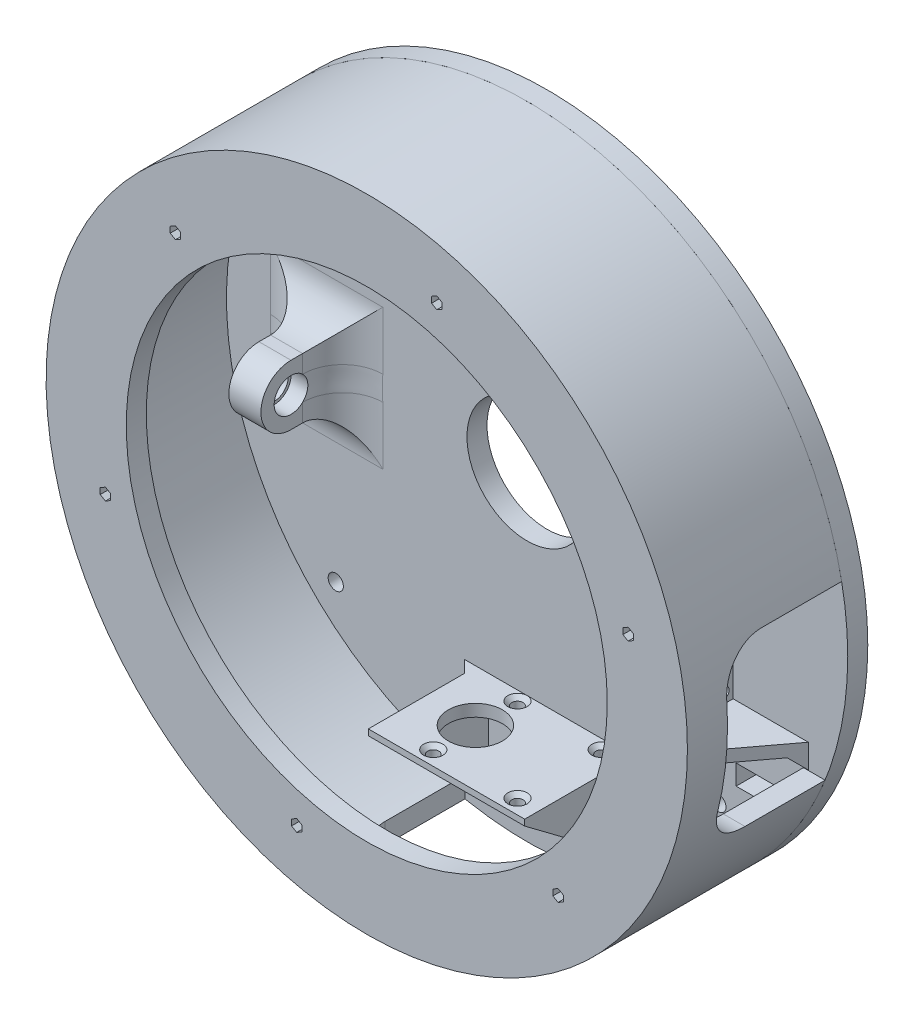
SolidWorks part; units mm, degrees
ref_plane "正面" through (0, 0, 0) normal (0, 0, 1) x (1, 0, 0)
ref_plane "平面" through (0, 0, 0) normal (0, 1, 0) x (1, 0, 0)
ref_plane "右側面" through (0, 0, 0) normal (1, 0, 0) x (0, 0, -1)
sketch "ｽｹｯﾁ5" plane through (0, 0, 0) normal (0, 1, 0) x (1, 0, 0)
  line L0 (48.4, -32) -> (48.4, 0)
  line L1 (48.4, 0) -> (72.4, 0)
  line L2 (72.4, 0) -> (48.4, -32)
  line L3 (-88, 0) -> (88, 0) construction
  dimension "D1" = 24
  dimension "D2" = 32
  dimension "D3" = 48.4
extrude "ﾎﾞｽ - 押し出し3" add sketch "ｽｹｯﾁ5" along normal blind 39 from offset 26.4 offset against normal yes
shell "ｼｪﾙ2" thickness 3
sketch "ｽｹｯﾁ7" plane through (51.4, 0, 0) normal (1, 0, 0) x (0, 0, -1)
  line L0 (-3, 9.6) -> (-3, -23.4) construction
  line L1 (-26.4, -21) -> (-5.4, -21) construction
  line L2 (-26.4, -21) -> (-26.4, 0) construction
  line L3 (-26.4, 0) -> (-5.4, 0) construction
  line L4 (-5.4, -21) -> (-5.4, 0) construction
  line L7 (-3, -23.4) -> (-28, -23.4) construction
  circle A0 centre (-15.9, 0) radius 6.75
  circle A1 centre (-26.4, -21) radius 1.4
  circle A2 centre (-5.4, -21) radius 1.4
  circle A3 centre (-5.4, 0) radius 1.4
  circle A4 centre (-26.4, 0) radius 1.4
  dimension "D3" = 2.8
  dimension "D6" = 13.5
  dimension "D1" = 21
  dimension "D2" = 21
  dimension "D4" = 2.4
  dimension "D5" = 2.4
extrude "ｶｯﾄ - 押し出し5" cut sketch "ｽｹｯﾁ7" against normal through all
sketch "ｽｹｯﾁ12" plane through (0, 0, 0) normal (0, 0, 1) x (1, 0, 0)
  line L0 (48.4, 12.6) -> (48.4, -26.4) construction
  line L1 (48.4, 12.6) -> (48.4, -26.4)
  line L2 (48.4, -26.4) -> (86.6023, -26.4)
  line L3 (72.4, -26.4) -> (48.4, -26.4) construction
  line L4 (86.6023, -26.4) -> (86.6023, 12.6)
  line L5 (86.6023, 12.6) -> (48.4, 12.6)
  line L6 (72.4, 12.6) -> (48.4, 12.6) construction
extrude "ｶｯﾄ - 押し出し14" cut sketch "ｽｹｯﾁ12" along normal blind 10 from offset 30
sketch "ｽｹｯﾁ18" plane through (48.4, 0, 0) normal (-1, 0, 0) x (0, 0, 1)
  circle A0 centre (26.4, 0) radius 2.4
  circle A1 centre (26.4, -21) radius 2.4
  circle A2 centre (5.4, 0) radius 2.4
  circle A3 centre (5.4, -21) radius 2.4
  dimension "D1" = 4.8
extrude "ｶｯﾄ - 押し出し15" cut sketch "ｽｹｯﾁ18" against normal blind 1.2 draft 45
sketch "ｽｹｯﾁ1" plane through (0, 0, 0) normal (0, 0, 1) x (1, 0, 0)
  line L1 (56.5685, -56.5685) -> (-56.5685, -56.5685) construction
  line L2 (56.5685, -56.5685) -> (56.5685, 56.5685) construction
  line L3 (56.5685, 56.5685) -> (-56.5685, 56.5685) construction
  line L4 (-56.5685, -56.5685) -> (-56.5685, 56.5685) construction
  line L5 (56.5685, -56.5685) -> (-56.5685, 56.5685) construction
  line L6 (56.5685, 56.5685) -> (-56.5685, -56.5685) construction
  circle A0 centre (0, 0) radius 80
  point P0 (0, 0)
  dimension "D1" = 160
extrude "ﾎﾞｽ - 押し出し1" add sketch "ｽｹｯﾁ1" along normal blind 3 and the other way blind 2 contours A0
sketch "ｽｹｯﾁ3" plane through (0, 0, 0) normal (0, 0, 1) x (1, 0, 0)
  circle A0 centre (0, 0) radius 15
  dimension "D1" = 30
extrude "ｶｯﾄ - 押し出し4" cut sketch "ｽｹｯﾁ3" against normal through all both and the other way through all
ref_plane "平面1" through (0, 54, 0) normal (0, 1, 0) x (1, 0, 0)
sketch "ｽｹｯﾁ10" plane through (-147.416, 54, 0) normal (0, 1, 0) x (1, 0, 0)
  line L0 (139.916, 0) -> (154.916, 0)
  line L1 (154.916, 0) -> (154.916, -15.9)
  line L2 (139.916, 0) -> (139.916, -15.9)
  line L3 (59.416, 0) -> (235.416, 0) construction
  arc A2 (139.916, -15.9) -> (154.916, -15.9) centre (147.416, -15.9) ccw
  point P7 (147.416, 0)
  dimension "D1" = 15
  dimension "D2" = 15.9
extrude "ﾎﾞｽ - 押し出し5" add sketch "ｽｹｯﾁ10" against normal blind 8
sketch "ｽｹｯﾁ11" plane through (-147.416, 54, 0) normal (0, 1, 0) x (1, 0, 0)
  circle A0 centre (147.416, -15.9) radius 4.2
  arc A1 (139.916, -15.9) -> (154.916, -15.9) centre (147.416, -15.9) ccw construction
  dimension "D1" = 8.4
extrude "ｶｯﾄ - 押し出し8" cut sketch "ｽｹｯﾁ11" along normal up to surface (8 mm away)
sketch "ｽｹｯﾁ14" plane through (0, 54, 0) normal (0, -1, 0) x (1, 0, 0)
  circle A0 centre (0, 15.9) radius 4.2 construction
  circle A1 centre (0, 15.9) radius 4.2
  circle A2 centre (0, 15.9) radius 3.5
  dimension "D1" = 7
extrude "ﾎﾞｽ - 押し出し6" add sketch "ｽｹｯﾁ14" along normal offset from surface (3.8 mm away) 4.2 up to face at (0, 46, 20.1)
fillet "ﾌｨﾚｯﾄ1" radius 10 4 edges at (7.5, 50, 3) (-7.5, 50, 3) (0, 46, 3) (0, 54, 3)
ref_plane "平面3" through (0, 0, 0) normal (0.7071, 0.7071, 0) x (-0.7071, 0.7071, 0)
mirror "ﾐﾗｰ1" about plane through (0, 0, 0) normal (0.7071, 0.7071, 0) of bodies 135 129
sketch "ｽｹｯﾁ15" plane through (0, 0, 3) normal (0, 0, 1) x (1, 0, 0)
  line L0 (-6.75, -51.4) -> (6.75, -51.4) construction
  line L1 (3.85, -68.1) -> (17.65, -68.1)
  line L2 (3.85, -68.1) -> (3.85, -74.4)
  line L3 (3.85, -74.4) -> (17.65, -74.4)
  line L4 (17.65, -68.1) -> (17.65, -74.4)
  line L5 (3.85, -68.1) -> (17.65, -74.4) construction
  line L6 (3.85, -74.4) -> (17.65, -68.1) construction
  line L7 (-6.75, -51.4) -> (6.75, -51.4)
  line L8 (88, -88) -> (-88, 88) construction
  line L9 (74.4, -3.85) -> (68.1, -17.65) construction
  line L10 (68.1, -3.85) -> (74.4, -17.65) construction
  line L11 (68.1, -17.65) -> (74.4, -17.65) construction
  line L12 (74.4, -3.85) -> (74.4, -17.65) construction
  line L13 (68.1, -3.85) -> (74.4, -3.85) construction
  line L14 (68.1, -3.85) -> (68.1, -17.65) construction
  point P0 (10.75, -71.25)
  point P7 (0, -51.4)
  point P14 (71.25, -10.75)
  dimension "D1" = 3.85
  dimension "D2" = 23
  dimension "D3" = 17.65
  dimension "D4" = 6.3
extrude "ｶｯﾄ - 押し出し11" cut sketch "ｽｹｯﾁ15" along normal through all both and the other way through all contours L12 L11 L14 L13 | L2 L1 L4 L3
sketch "ｽｹｯﾁ16" plane through (0, 0, 3) normal (0, 0, 1) x (1, 0, 0)
  line L0 (56.5685, 56.5685) -> (-56.5685, -56.5685) construction
  circle A0 centre (0, 0) radius 67.5 construction
  circle A1 centre (-47.7297, -47.7297) radius 1.9
  circle A3 centre (-47.7297, 47.7297) radius 1.9
  circle A4 centre (47.7297, 47.7297) radius 1.9
  circle A5 centre (47.7297, -47.7297) radius 1.9
  point P14 (0, 0)
  dimension "D1" = 135
  dimension "D3" = 3.8
  dimension "D2" = 4
extrude "ｶｯﾄ - 押し出し12" cut sketch "ｽｹｯﾁ16" against normal through all both and the other way through all
chamfer "面取り1" distance 3 angle 45 4 edges at (-12.6, -59.275, 3) (26.4, -59.275, 3) (59.275, -26.4, 3) (59.275, 12.6, 3)
sketch "ｽｹｯﾁ17" plane through (0, 0, 3) normal (0, 0, 1) x (1, 0, 0)
  line L1 (62.15, -41.9) -> (52.15, -41.9)
  line L2 (62.15, -41.9) -> (62.15, -36.9)
  line L3 (62.15, -36.9) -> (52.15, -36.9)
  line L4 (52.15, -41.9) -> (52.15, -36.9)
  line L5 (62.15, -41.9) -> (52.15, -36.9) construction
  line L6 (62.15, -36.9) -> (52.15, -41.9) construction
  line L7 (48.4, -26.4) -> (67.9, -26.4) construction
  line L8 (70.15, -23.4) -> (70.15, -29.4) construction
  point P0 (57.15, -39.4)
  dimension "D1" = 5
  dimension "D2" = 13
  dimension "D3" = 10
  dimension "D4" = 8
extrude "ｶｯﾄ - 押し出し13" cut sketch "ｽｹｯﾁ17" against normal blind 10
sketch "ｽｹｯﾁ19" plane through (0, 0, 3) normal (0, 0, 1) x (1, 0, 0)
  circle A0 centre (0, 0) radius 80 construction
  circle A1 centre (0, 0) radius 80
  circle A2 centre (0, 0) radius 75
  dimension "D1" = 5
extrude "ﾎﾞｽ - 押し出し7" add sketch "ｽｹｯﾁ19" along normal blind 35 separate body
sketch "ｽｹｯﾁ22" plane through (0, 54, 0) normal (0, 1, 0) x (1, 0, 0)
  line L8 (-15.6, -3) -> (0, -3) construction
  line L9 (-15.5, -3) -> (29.5, -3)
  line L10 (-15.5, -3) -> (-15.5, -33)
  line L11 (-15.5, -33) -> (29.5, -33)
  line L12 (29.5, -3) -> (29.5, -33)
  line L13 (-15.5, -3) -> (29.5, -33) construction
  line L14 (-15.5, -33) -> (29.5, -3) construction
  line L15 (56.5685, 0) -> (-56.5685, 0) construction
  point P2 (7, -18)
  point P9 (0, 0)
  dimension "D1" = 7
  dimension "D2" = 45
  dimension "D3" = 30
extrude "ｶｯﾄ - 押し出し17" cut sketch "ｽｹｯﾁ22" against normal through all
fillet "ﾌｨﾚｯﾄ2" radius 10 2 edges at (-15.5, -75.9325, 33) (29.5, -71.6585, 33)
mirror "ﾐﾗｰ2" about plane through (0, 0, 0) normal (0.7071, 0.7071, 0) of "ｶｯﾄ - 押し出し17", "ﾌｨﾚｯﾄ2"
sketch "ｽｹｯﾁ23" plane through (0, 0, 38) normal (0, 0, 1) x (1, 0, 0)
  circle A0 centre (0, 0) radius 60
  circle A1 centre (0, 0) radius 15 construction
  circle A3 centre (0, 0) radius 80
  circle A4 centre (0, 0) radius 80
  dimension "D1" = 120
  dimension "D2" = 0
extrude "ﾎﾞｽ - 押し出し8" add sketch "ｽｹｯﾁ23" along normal blind 5
sketch "ｽｹｯﾁ24" plane through (0, 0, 43) normal (0, 0, 1) x (1, 0, 0)
  line L0 (56.5685, -56.5685) -> (-56.5685, 56.5685) construction
  line L1 (-47.7297, 46.2286) -> (-46.4297, 46.9792)
  line L2 (-46.4297, 46.9792) -> (-46.4297, 48.4803)
  line L3 (-46.4297, 48.4803) -> (-47.7297, 49.2308)
  line L4 (-47.7297, 49.2308) -> (-49.0297, 48.4803)
  line L5 (-49.0297, 48.4803) -> (-49.0297, 46.9792)
  line L6 (-49.0297, 46.9792) -> (-47.7297, 46.2286)
  line L7 (16.1703, 64.4494) -> (17.4703, 63.6989)
  line L8 (17.4703, 63.6989) -> (18.7703, 64.4494)
  line L9 (18.7703, 64.4494) -> (18.7703, 65.9505)
  line L10 (18.7703, 65.9505) -> (17.4703, 66.7011)
  line L11 (17.4703, 66.7011) -> (16.1703, 65.9505)
  line L12 (16.1703, 65.9505) -> (16.1703, 64.4494)
  line L13 (63.9, 18.2208) -> (63.9, 16.7197)
  line L14 (63.9, 16.7197) -> (65.2, 15.9692)
  line L15 (65.2, 15.9692) -> (66.5, 16.7197)
  line L16 (66.5, 16.7197) -> (66.5, 18.2208)
  line L17 (66.5, 18.2208) -> (65.2, 18.9714)
  line L18 (65.2, 18.9714) -> (63.9, 18.2208)
  line L19 (47.7297, -46.2286) -> (46.4297, -46.9792)
  line L20 (46.4297, -46.9792) -> (46.4297, -48.4803)
  line L21 (46.4297, -48.4803) -> (47.7297, -49.2308)
  line L22 (47.7297, -49.2308) -> (49.0297, -48.4803)
  line L23 (49.0297, -48.4803) -> (49.0297, -46.9792)
  line L24 (49.0297, -46.9792) -> (47.7297, -46.2286)
  line L25 (-16.1703, -64.4494) -> (-17.4703, -63.6989)
  line L26 (-17.4703, -63.6989) -> (-18.7703, -64.4494)
  line L27 (-18.7703, -64.4494) -> (-18.7703, -65.9505)
  line L28 (-18.7703, -65.9505) -> (-17.4703, -66.7011)
  line L29 (-17.4703, -66.7011) -> (-16.1703, -65.9505)
  line L30 (-16.1703, -65.9505) -> (-16.1703, -64.4494)
  line L31 (-63.9, -18.2208) -> (-63.9, -16.7197)
  line L32 (-63.9, -16.7197) -> (-65.2, -15.9692)
  line L33 (-65.2, -15.9692) -> (-66.5, -16.7197)
  line L34 (-66.5, -16.7197) -> (-66.5, -18.2208)
  line L35 (-66.5, -18.2208) -> (-65.2, -18.9714)
  line L36 (-65.2, -18.9714) -> (-63.9, -18.2208)
  circle A0 centre (0, 0) radius 67.5 construction
  circle A1 centre (0, 0) radius 15 construction
  circle A2 centre (-47.7297, 47.7297) radius 1.3 construction
  point P5 (87.7346, 0)
  point P16 (0, 0)
  point P29 (0, 0)
  dimension "D1" = 135
  dimension "D2" = 2.6
  dimension "D3" = 6
extrude "ｶｯﾄ - 押し出し18" cut sketch "ｽｹｯﾁ24" against normal through all
chamfer "面取り2" distance 2 angle 45 1 edges at (75, 0, 38)
equation "\"ー２\"=2"
